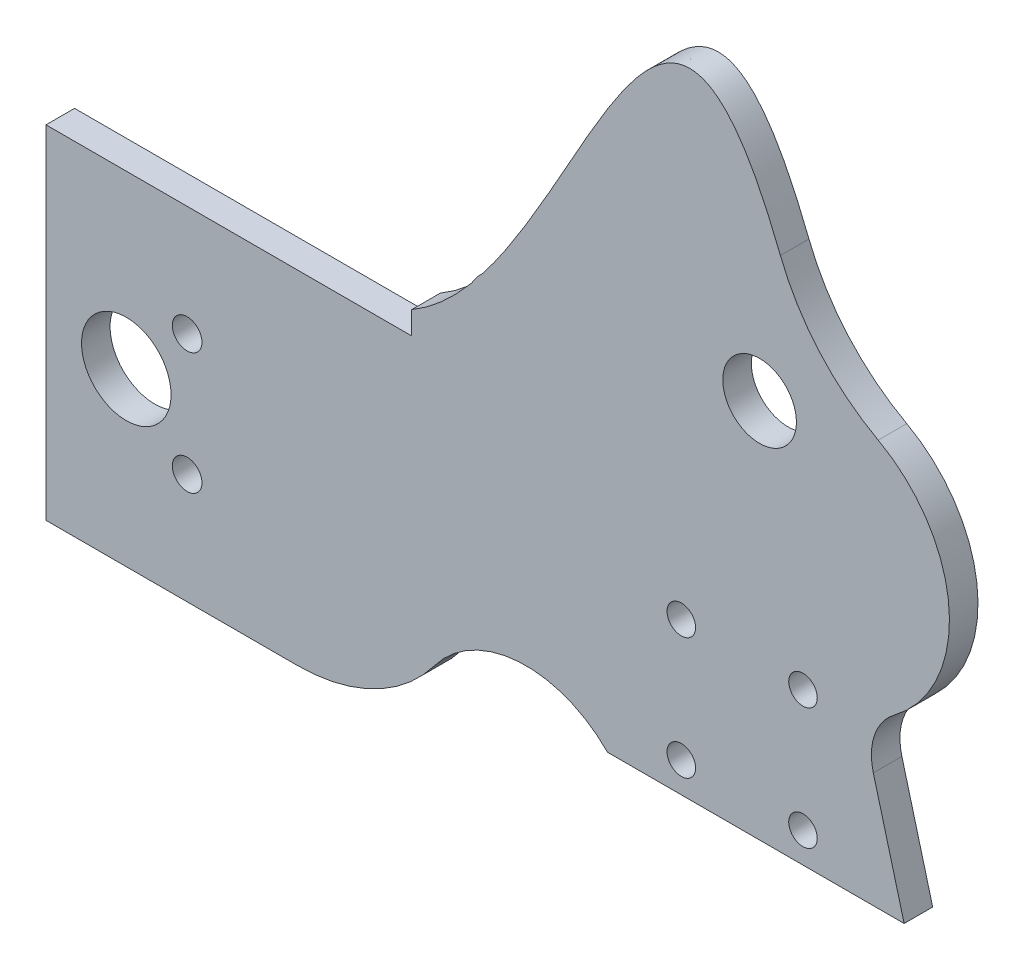
SolidWorks part; units mm, degrees
ref_plane "Front Plane" through (0, 0, 0) normal (0, 0, 1) x (1, 0, 0)
ref_plane "Top Plane" through (0, 0, 0) normal (0, 1, 0) x (1, 0, 0)
ref_plane "Right Plane" through (0, 0, 0) normal (1, 0, 0) x (0, 0, -1)
sketch "Sketch1" plane through (0, 0, 0) normal (0, 0, 1) x (1, 0, 0)
  line L0 (0, 0) -> (107.95, 0)
  line L3 (0, 38.1) -> (0, 25.4)
  line L4 (95.3675, 55.88) -> (0, 38.1)
  line L5 (0, 19.05) -> (100.2273, 19.05) construction
  line L6 (19.05, 19.05) -> (19.05, 28.62) construction
  line L7 (19.05, 19.05) -> (25.817, 25.817) construction
  line L8 (107.95, 0) -> (100.9363, 26.1756)
  line L10 (0, 12.7) -> (0, 0)
  line L11 (0, 25.4) -> (-7.62, 25.4)
  line L13 (0, 12.7) -> (-7.62, 12.7)
  line L14 (-7.62, 25.4) -> (-7.62, 12.7)
  line L15 (100.9363, 26.1756) -> (100.8688, 26.4276)
  arc A0 (100.8688, 26.4276) -> (95.3675, 55.88) centre (95.3675, 40.64) ccw
  circle A1 centre (95.3675, 40.64) radius 4.0957 construction
  circle A2 centre (19.05, 19.05) radius 9.57 construction
  circle A3 centre (25.817, 25.817) radius 1.651
  circle A4 centre (25.817, 12.283) radius 1.651
  circle A7 centre (12.283, 12.283) radius 1.651 [skipped]
  circle A8 centre (12.283, 25.817) radius 1.651 [skipped]
  point P26 (19.05, 19.05)
  dimension "D1" = 8.1915
  dimension "D5" = 15.24
  dimension "D4" = 19.14
  dimension "D7" = 3.302
  dimension "D11" = 97.0107
  dimension "D2" = 38.1
  dimension "D3" = 40.64
  dimension "D6" = 107.95
  dimension "D8" = 45
  dimension "D9" = 4
  dimension "D10" = 19.05
  dimension "D12" = 75
  dimension "D14" = 12.7
  dimension "D15" = 12.7
  dimension "D16" = 7.62
extrude "Boss-Extrude1" add sketch "Sketch1" along normal blind 3.175
sketch "Sketch2" plane through (0, 0, 3.175) normal (0, 0, 1) x (1, 0, 0)
  circle A0 centre (95.3675, 40.64) radius 38.1 construction
sketch "Sketch6" plane through (0, 0, 3.175) normal (0, 0, 1) x (1, 0, 0)
  line L0 (0, 0) -> (107.95, 0) construction
  line L1 (50.8, 0) -> (76.2, 0)
  arc A0 (76.2, 0) -> (50.8, 0) centre (63.5, 0) ccw
  dimension "D1" = 25.4
  dimension "D2" = 31.75
extrude "Cut-Extrude2" cut sketch "Sketch6" against normal blind 6.35
sketch "Sketch7" plane through (0, 0, 3.175) normal (0, 0, 1) x (1, 0, 0)
  line L0 (12.283, 25.817) -> (25.817, 12.283) construction
  line L1 (12.283, 12.283) -> (25.817, 25.817) construction
  circle A0 centre (19.05, 19.05) radius 4.9784
  circle A2 centre (80.7829, 12.2536) radius 1.5875
  circle A3 centre (94.316, 12.2536) radius 1.5875
  circle A4 centre (80.7829, 25.7876) radius 1.5875
  circle A5 centre (94.316, 25.7876) radius 1.5875
  dimension "D1" = 9.9568
extrude "Cut-Extrude3" cut sketch "Sketch7" against normal through all
fillet "Fillet1" radius 6.35 1 edges at (100.8688, 26.4276, 1.5875)
sketch "Sketch8" plane through (0, 0, 3.175) normal (0, 0, 1) x (1, 0, 0)
  line L1 (0, 38.1) -> (50.8, 38.1)
  line L2 (0, 38.1) -> (0, 50.8)
  line L3 (0, 50.8) -> (50.8, 50.8)
  line L4 (50.8, 38.1) -> (50.8, 50.8)
  dimension "D1" = 50.8
  dimension "D2" = 12.7
extrude "Cut-Extrude4" cut sketch "Sketch8" against normal blind 50.8
sketch "Sketch9" plane through (0, 0, 3.175) normal (0, 0, 1) x (1, 0, 0)
  line L3 (50.8, 40.64) -> (57.15, 40.64)
  line L5 (57.15, 40.64) -> (50.8, 40.64)
  line L6 (57.15, 40.64) -> (57.15, 50.8)
  line L7 (57.15, 50.8) -> (50.8, 50.8)
  line L8 (50.8, 40.64) -> (50.8, 50.8)
  line L9 (0, 38.1) -> (50.8, 38.1) construction
  line M8 (50.8, 47.571) -> (50.8, 38.1)
  line M21 (95.3675, 55.88) -> (50.8, 47.571)
  dimension "D1" = 10.16
  dimension "D2" = 2.54
  dimension "D3" = 6.35
extrude "Cut-Extrude5" cut sketch "Sketch9" against normal blind 19.304 contours L3 L6 M21 M8 region at (54.0583, 44.4092, 3.175)
fillet "Fillet6" radius 6.35 1 edges at (57.15, 40.64, 1.5875)
fillet "Fillet7" radius 6.35 1 edges at (57.15, 48.7549, 1.5875)
fillet "Fillet8" radius 19.05 1 edges at (50.8, 0, 1.5875)
sketch "Sketch12" plane through (0, 0, 3.175) normal (0, 0, 1) x (1, 0, 0)
  line L0 (107.95, 0) -> (146.812, 0) construction
  line L1 (8.0257, 45.4128) -> (80.6683, 75.7903) construction
  line L2 (95.3675, 40.64) -> (80.6683, 75.7903) construction
  line L3 (80.6683, 75.7903) -> (79.4434, 78.7195) construction
  line L4 (50.8, 40.64) -> (85.0271, 40.64)
  line L5 (85.0271, 40.64) -> (95.3675, 55.88)
  arc A0 (61.8128, 49.6242) -> (56.8883, 45.1859) centre (62.9766, 43.3817) ccw construction
  circle A1 centre (19.05, 19.05) radius 28.575 construction
  circle A2 centre (95.3675, 40.64) radius 38.1 construction
  circle A3 centre (80.6683, 75.7903) radius 3.175 construction
  spline S0 degree 3 poles (50.8, 40.64) (70.7778, 52.1788) (78.5943, 111.5434) (95.3675, 55.88) knots 0 0 0 0 1 1 1 1
  dimension "D2" = 6.35
  dimension "D1" = 38.862
extrude "Boss-Extrude2" add sketch "Sketch12" against normal blind 3.175
fillet "Fillet9" radius 24.13 1 edges at (95.3675, 55.88, 1.5875)
sketch "Sketch13" plane through (0, 38.1, 0) normal (0, 1, 0) x (1, 0, 0)
  line L0 (10.12, -3.175) -> (10.12, 0)
  line L1 (0, -3.175) -> (50.8, -3.175) construction
  line L2 (0, 0) -> (50.8, 0) construction
extrude "Cut-Extrude6" cut sketch "Sketch13" against normal through all
sketch "Sketch14" plane through (0, 0, 3.175) normal (0, 0, 1) x (1, 0, 0)
  circle A0 centre (89.49, 51.1876) radius 4.0958
  circle A1 centre (94.316, 25.7876) radius 1.5875 construction
  circle A2 centre (95.3675, 40.64) radius 4.0957 construction
  dimension "D1" = 4.826
  dimension "D2" = 25.4
extrude "Cut-Extrude7" cut sketch "Sketch14" against normal through all
sketch "Sketch17" plane through (0, 0, 3.175) normal (0, 0, 1) x (1, 0, 0)
  line L0 (76.2, 0) -> (107.95, 0) construction
  line L1 (64.0585, 8.89) -> (108.994, 8.89)
  line L2 (64.0585, 8.89) -> (64.0585, 0)
  line L3 (64.0585, 0) -> (108.994, 0)
  line L4 (108.994, 8.89) -> (108.994, 0)
  point P4 (64.0585, -0.9797)
  dimension "D1" = 8.89
extrude "Cut-Extrude10" cut sketch "Sketch17" against normal through all
